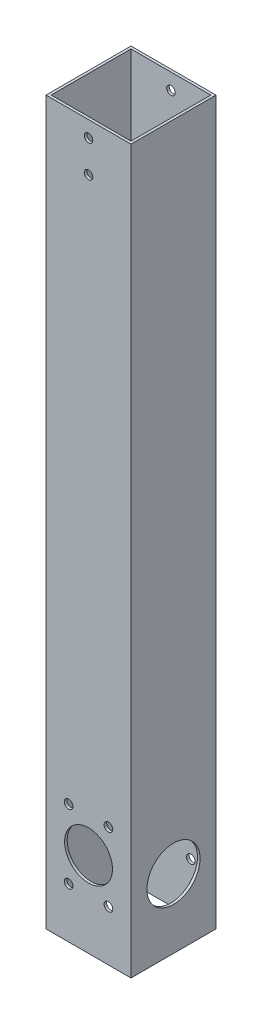
SolidWorks part; units mm, degrees
material "6061 Alloy"
ref_plane "Front Plane" through (0, 0, 0) normal (0, 0, 1) x (1, 0, 0)
ref_plane "Top Plane" through (0, 0, 0) normal (0, 1, 0) x (1, 0, 0)
ref_plane "Right Plane" through (0, 0, 0) normal (1, 0, 0) x (0, 0, -1)
sketch "Sketch1" plane through (0, 0, 0) normal (0, 1, 0) x (1, 0, 0)
  line L1 (25.4, 25.4) -> (-25.4, 25.4)
  line L2 (25.4, 25.4) -> (25.4, -25.4)
  line L3 (25.4, -25.4) -> (-25.4, -25.4)
  line L4 (-25.4, 25.4) -> (-25.4, -25.4)
  line L5 (25.4, 25.4) -> (-25.4, -25.4) construction
  line L6 (25.4, -25.4) -> (-25.4, 25.4) construction
  point P0 (0, 0)
  dimension "D1" = 50.8
extrude "Extrude-Thin1" add sketch "Sketch1" along normal blind 431.8 thin thin type one direction reverse wall 1.524
sketch "Sketch2" plane through (0, 0, 0) normal (0, 0, 1) x (1, 0, 0)
  line L0 (-36.2563, 68.2625) -> (38.5702, 68.2625) construction
  line L1 (-25.4, 0) -> (25.4, 0) construction
  line L2 (-25.4, 50.8) -> (25.4, 50.8) construction
  line L6 (25.4, 431.8) -> (25.4, 0) construction
  line L7 (-25.4, 431.8) -> (-25.4, 0) construction
  line L8 (-11.9062, 30.1778) -> (11.9063, 30.1778) construction
  line L9 (-11.9062, 71.4222) -> (11.9063, 71.4222) construction
  circle A0 centre (0, 50.8) radius 14.3002
  circle A1 centre (0, 50.8) radius 23.8125 construction
  circle A2 centre (-11.9062, 30.1778) radius 2.5908
  circle A3 centre (11.9063, 30.1778) radius 2.5908
  circle A4 centre (11.9063, 71.4222) radius 2.5908
  circle A5 centre (-11.9062, 71.4222) radius 2.5908
  point P11 (0, 50.8)
  dimension "D1" = 28.6004
  dimension "D3" = 17.4625
  dimension "D4" = 47.625
  dimension "D6" = 5.1816
  dimension "D2" = 50.8
  dimension "D5" = 60
extrude "Cut-Extrude1" cut sketch "Sketch2" along normal through all both and the other way through all
sketch "Sketch3" plane through (25.4, 0, 0) normal (1, 0, 0) x (0, 0, -1)
  line L0 (-25.4, 50.8) -> (25.4, 50.8) construction
  line L1 (-25.4, 65.1002) -> (-25.4, 36.4998) construction
  line L3 (25.4, 431.8) -> (25.4, 0) construction
  circle A0 centre (0, 41.275) radius 15.875
  point P9 (0, 50.8)
  dimension "D1" = 31.75
  dimension "D2" = 9.525
extrude "Cut-Extrude2" cut sketch "Sketch3" against normal up to surface (1.524 mm away) up to face at (23.876, 215.9, 0)
sketch "Sketch4" plane through (0, 0, 25.4) normal (0, 0, 1) x (1, 0, 0)
  line L0 (-25.4, 431.8) -> (25.4, 431.8) construction
  circle A0 centre (0, 422.275) radius 2.54
  circle A1 centre (0, 403.225) radius 2.54
  point P4 (0, 0)
  point P6 (0, 0)
  dimension "D1" = 5.08
  dimension "D2" = 9.525
  dimension "D3" = 28.575
hole_wizard "#10 Clearance Hole1" positions "Sketch5" profile "Sketch6" hole size "#10" standard "ANSI Inch" end condition through all
sketch "Sketch5" plane through (0, 0, 25.4) normal (0, 0, 1) x (1, 0, 0)
  point P0 (0, 403.225)
  point P3 (0, 422.275)
sketch "Sketch6" plane through (0, 403.225, 25.4) normal (1, 0, 0) x (0, -1, 0)
  line L0 (0, 0) -> (0, 50.8)
  line L1 (0, 50.8) -> (2.5527, 50.8)
  line L2 (2.5527, 50.8) -> (2.5527, 0)
  line L5 (2.5527, 0) -> (0, 0)
  line L11 (0, -6.35) -> (0, 107.95) construction
  dimension "Thru Hole Dia." = 5.1054
  dimension "Thru Hole Depth" = 50.8
